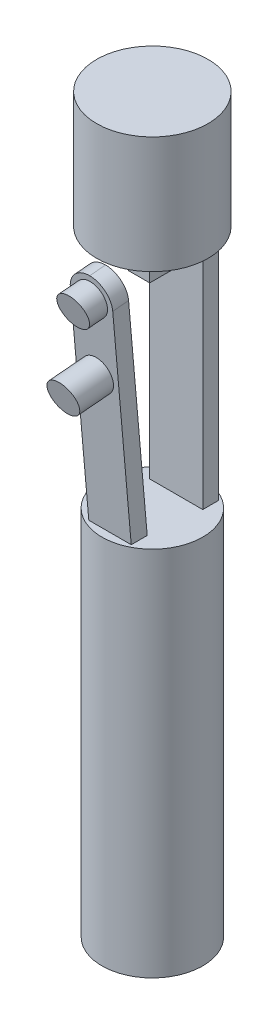
SolidWorks part; units mm, degrees
ref_plane "Front Plane" through (0, 0, 0) normal (0, 0, 1) x (1, 0, 0)
ref_plane "Top Plane" through (0, 0, 0) normal (0, 1, 0) x (1, 0, 0)
ref_plane "Right Plane" through (0, 0, 0) normal (1, 0, 0) x (0, 0, -1)
sketch "Sketch1" plane through (0, 0, 0) normal (0, 1, 0) x (1, 0, 0)
  circle A0 centre (0, 0) radius 5.25
  dimension "D1" = 10.5
extrude "Boss-Extrude1" add sketch "Sketch1" against normal blind 11
sketch "Sketch2" plane through (0, -11, 0) normal (0, -1, 0) x (1, 0, 0)
  line L2 (-2.5, -2.25) -> (2.5, -2.25)
  line L3 (-2.5, -2.25) -> (-2.5, -3.75)
  line L4 (-2.5, -3.75) -> (2.5, -3.75)
  line L5 (2.5, -2.25) -> (2.5, -3.75)
  line L6 (0, -3.75) -> (0, -2.25) construction
  line L7 (-2.5, -3) -> (2.5, -3) construction
  line L8 (1.25, -4.25) -> (-1.25, -4.25)
  line L9 (1.25, -4.25) -> (1.25, -3.75)
  line L10 (1.25, -3.75) -> (-1.25, -3.75)
  line L11 (-1.25, -4.25) -> (-1.25, -3.75)
  line L12 (0, -3.75) -> (0, -4.25) construction
  line L13 (1.25, -4) -> (-1.25, -4) construction
  circle A4 centre (0, 0) radius 5.25 construction
  point P0 (0, -3)
  point P9 (0, -4)
  dimension "D1" = 1.5
  dimension "D2" = 3
  dimension "D3" = 5
  dimension "D4" = 2.5
  dimension "D5" = 0.5
extrude "Boss-Extrude2" add sketch "Sketch2" along normal blind 23 contours L5 L2 L3 L4 | L11 L8 L9 L4 region at (0, -11, -3) region at (0, -11, -4)
sketch "Sketch3" plane through (0, 0, 0) normal (1, 0, 0) x (0, 0, -1)
  line L0 (2.25, -14.5) -> (-1.25, -14.5)
  line L2 (-1.25, -14.5) -> (-1.25, -11)
  line L3 (-5.25, -11) -> (5.25, -11) construction
  line L4 (-1.25, -11) -> (2.25, -11)
  line L5 (2.25, -11) -> (2.25, -14.5)
  line L6 (2.25, -34) -> (2.25, -11) construction
  point P4 (0, 0)
  point P9 (0, 0)
  dimension "D1" = 3.5
  dimension "D2" = 3.5
extrude "Boss-Extrude3" add sketch "Sketch3" along normal mid plane 2
sketch "Sketch6" plane through (0, -34, 0) normal (0, -1, 0) x (1, 0, 0)
  circle A0 centre (0, 0) radius 4.75
  dimension "D1" = 9.5
extrude "Boss-Extrude5" add sketch "Sketch6" along normal blind 35
sketch "Sketch7" plane through (0, -69, 0) normal (0, -1, 0) x (1, 0, 0)
  circle A0 centre (0, 0) radius 3.25
  circle A1 centre (0, 0) radius 4.75 construction
  dimension "D1" = 1.5
extrude "Cut-Extrude2" cut sketch "Sketch7" against normal offset from surface (1.5 mm away) 1.5 up to face at (0, -34, -3.5)
sketch "Sketch8" plane through (0, -69, 0) normal (0, -1, 0) x (1, 0, 0)
  line L0 (0, 3.25) -> (0, -3.25) construction
  line L1 (-3.25, 0) -> (3.25, 0) construction
  line L3 (-4.15, 0.4) -> (-2.35, 0.4)
  line L4 (-4.15, 0.4) -> (-4.15, -0.4)
  line L5 (-4.15, -0.4) -> (-2.35, -0.4)
  line L6 (-2.35, 0.4) -> (-2.35, -0.4)
  line L7 (-3.25, -0.4) -> (-3.25, 0.4) construction
  line L8 (-4.15, 0) -> (-2.35, 0) construction
  circle A0 centre (0, 0) radius 3.25 construction
  circle A1 centre (0, 0) radius 3.25 construction
  dimension "D1" = 0.8
  dimension "D2" = 1.8
extrude "Boss-Extrude6" add sketch "Sketch8" against normal blind 8
pattern_circular "CirPattern1" count 4 over 360 about axis through (0, -69, 0) along (0, -1, 0) of "Boss-Extrude6"
sketch "Sketch10" plane through (0, 0, 0) normal (1, 0, 0) x (0, 0, -1)
  line L0 (-3.2378, -34) -> (-5.25, -11) construction
  line L1 (4.75, -34) -> (-4.75, -34) construction
  line L2 (-5.25, 0) -> (-5.25, -11) construction
  line L3 (-3.2378, -34) -> (-3.9906, -34)
  line L4 (-3.9906, -34) -> (-5.9081, -12.0837)
  line L5 (-5.9081, -12.0837) -> (-4.4138, -11.953)
  line L6 (-4.4138, -11.953) -> (-2.4849, -34)
  line L7 (-2.4849, -34) -> (-3.2378, -34)
  point P5 (-5.1609, -12.0183)
  dimension "D1" = 5
  dimension "D2" = 22
  dimension "D3" = 1.5
extrude "Boss-Extrude7" add sketch "Sketch10" along normal mid plane 4
fillet "Fillet1" radius 2 2 edges at (2, -12.0183, 5.1609) (-2, -12.0183, 5.1609)
sketch "Sketch12" plane through (0, 0, 0) normal (1, 0, 0) x (0, 0, -1)
  line L0 (-1.9849, -34) -> (-4.0651, -15.9378)
  line L1 (4.75, -34) -> (-4.75, -34) construction
  line L2 (-1.9849, -34) -> (-2.4849, -34)
  line L4 (-2.4849, -34) -> (-4.0651, -15.9378)
  line L5 (-4.2394, -13.9454) -> (-4.4138, -11.953) construction
  point P5 (0, 0)
  point P8 (-4.1295, -14.0027)
  point P10 (-1.5242, -16.2197)
  dimension "D1" = 0.5
  dimension "D2" = 4
extrude "Boss-Extrude8" add sketch "Sketch12" along normal mid plane 1
sketch "Sketch13" plane through (0, -0.6048, 6.9123) normal (0, -0.0872, 0.9962) x (1, 0, 0)
  circle A0 centre (0, -13.5228) radius 1.5
  dimension "D1" = 3
extrude "Boss-Extrude9" add sketch "Sketch13" along normal blind 2
sketch "Sketch14" plane through (0, -0.6048, 6.9123) normal (0, -0.0872, 0.9962) x (1, 0, 0)
  circle A0 centre (0, -20.0228) radius 1.5
  circle A1 centre (0, -13.5228) radius 1.5 construction
  point P4 (0, 0)
  point P5 (0, -20.0228)
  point P6 (0, 0)
  point P7 (0, -20.0228)
  dimension "D1" = 3
  dimension "D2" = 3.5
extrude "Boss-Extrude10" add sketch "Sketch14" along normal blind 3.5
sketch "Sketch15" plane through (0, 0, 0) normal (1, 0, 0) x (0, 0, -1)
  line L0 (-8.7846, -19.3621) -> (-7.9962, -22.3046)
  line L1 (-8.5232, -22.3507) -> (-5.0365, -22.0457) construction
  line L2 (-7.9962, -22.3046) -> (-8.5232, -22.3507)
  line L3 (-8.5232, -22.3507) -> (-8.7846, -19.3621)
  dimension "D1" = 10
extrude "Cut-Extrude3" cut sketch "Sketch15" against normal through all and the other way through all
sketch "Sketch16" plane through (0, 0, 0) normal (1, 0, 0) x (0, 0, -1)
  line L0 (-7.8569, -12.7561) -> (-7.0684, -15.6986)
  line L1 (-7.5954, -15.7447) -> (-5.603, -15.5704) construction
  line L2 (-7.0684, -15.6986) -> (-7.5954, -15.7447)
  line L3 (-7.5954, -15.7447) -> (-7.8569, -12.7561)
  dimension "D1" = 10
extrude "Cut-Extrude4" cut sketch "Sketch16" against normal through all and the other way through all
